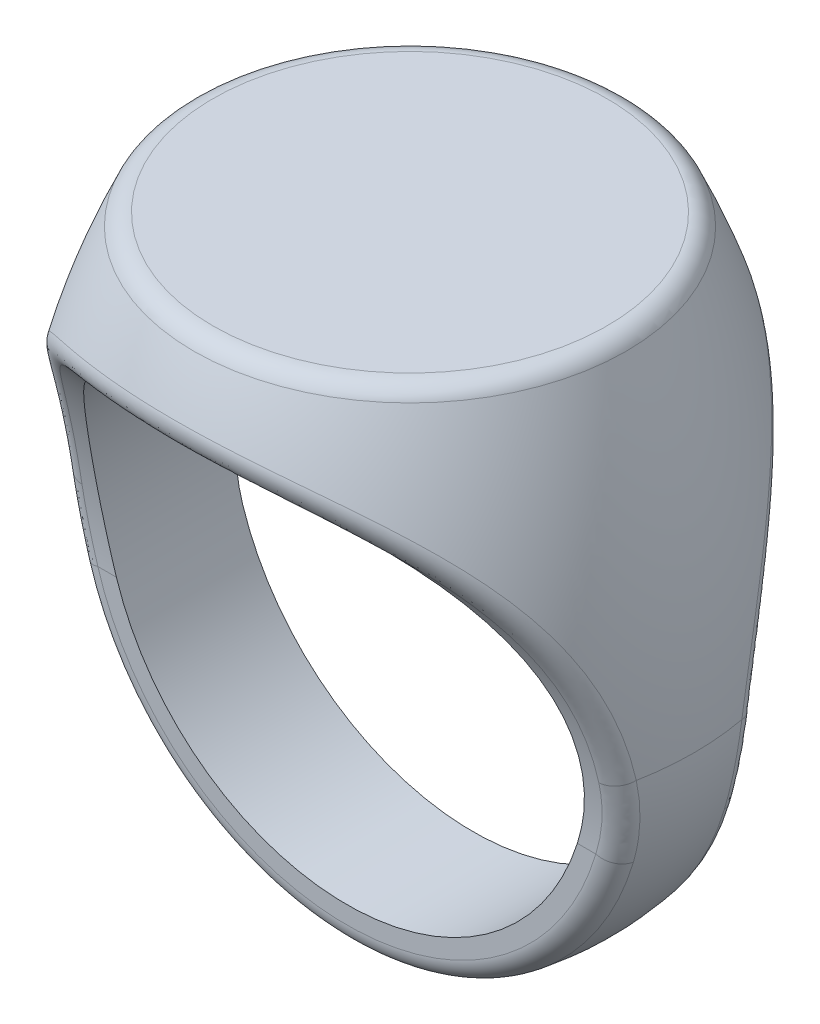
SolidWorks part; units mm, degrees
note: The reader was unsure of these and kept them because the rebuilt part matched: shared geometry of "Sketch1<5>".
ref_plane "Front Plane" through (0, 0, 0) normal (0, 0, 1) x (1, 0, 0)
ref_plane "Top Plane" through (0, 0, 0) normal (0, 1, 0) x (1, 0, 0)
ref_plane "Right Plane" through (0, 0, 0) normal (1, 0, 0) x (0, 0, -1)
sketch "Sketch1" plane through (0, 0, 0) normal (0, 0, 1) x (1, 0, 0)
  line L0 (-10, 15.5) -> (10, 15.5)
  line L1 (0, 15.5) -> (0, -13.5)
  circle A0 centre (0, 0) radius 11.5
  circle A1 centre (0, 0) radius 13.5
  arc A2 (-13.5, 0) -> (-10, 15.5) centre (22.5714, 0) cw
  arc A3 (10, 15.5) -> (13.5, 0) centre (-22.5714, 0) cw
  point P7 (0, 15.5)
  dimension "D1" = 23
  dimension "D3" = 20
  dimension "D4" = 2
  dimension "D2" = 2
revolve "Revolve1" add sketch "Sketch1" angle 360 about L1
sketch "Sketch2" plane through (0, 0, 0) normal (1, 0, 0) x (0, 0, -1)
  line L0 (0, 11.5) -> (0, -11.5) construction
  line L1 (0, 15.5) -> (0, 0) construction
  line L2 (0, 11.5) -> (0, -11.5)
  line L3 (0, 15.5) -> (0, 0)
  line L4 (0, 13.5) -> (0, -13.5) construction
  line L5 (0, 13.5) -> (0, -13.5)
  line L6 (10, 15.5) -> (-10, 15.5)
  line L7 (10, 15.5) -> (11, 11.5)
  line L8 (3, -3.5) -> (3, -13.5)
  line L9 (3, -13.5) -> (-3, -13.5)
  line L10 (-3, -3.5) -> (-3, -13.5)
  line L13 (13.5, 0) -> (-13.5, 0)
  line L14 (13.5, 0) -> (-13.5, 0)
  arc A0 (11, 11.5) -> (3, -3.5) centre (21.0625, -3.5) ccw
  arc A1 (-11.5059, 11.8273) -> (-3, -3.5) centre (-21.0625, -3.5) cw
  arc A2 (-10, 15.5) -> (-13.5, 0) centre (22.5714, 0) ccw construction
  arc A3 (-10, 15.5) -> (-13.5, 0) centre (22.5714, 0) ccw
  arc A4 (-13.5, 0) -> (13.5, 0) centre (0, 0) ccw construction
  arc A5 (-13.5, 0) -> (13.5, 0) centre (0, 0) ccw
  point P8 (0, 15.5)
  point P13 (0, 0)
  point P15 (0, 0)
  dimension "D1" = 20
  dimension "D2" = 10
  dimension "D3" = 3
  dimension "D4" = 11
  dimension "D5" = 4
  dimension "D6" = 0
extrude "Cut-Extrude1" cut sketch "Sketch2" against normal through all both and the other way through all contours L14 A5 L10 A1 | A1 A3 L14
mirror "Mirror1" about plane through (0, 0, 0) normal (0, 0, 1) of "Cut-Extrude1"
extrude "Cut-Extrude2" cut sketch "Sketch1<5>" against normal through all both and the other way through all contours L1 A0 | L1 A0
sketch "Sketch1<5>" plane through (0, 0, 0) normal (0, 0, 1) x (1, 0, 0) same geometry as "Sketch1"
fillet "Fillet1" radius 1 8 edges at (0, -13.1624, 3) (0, -13.1624, -3) (-0.0532, 11.8272, 11.5058) (-0.0532, 11.8272, -11.5058)
fillet "Fillet2" radius 1 1 edges at (0, 15.5, 10)
